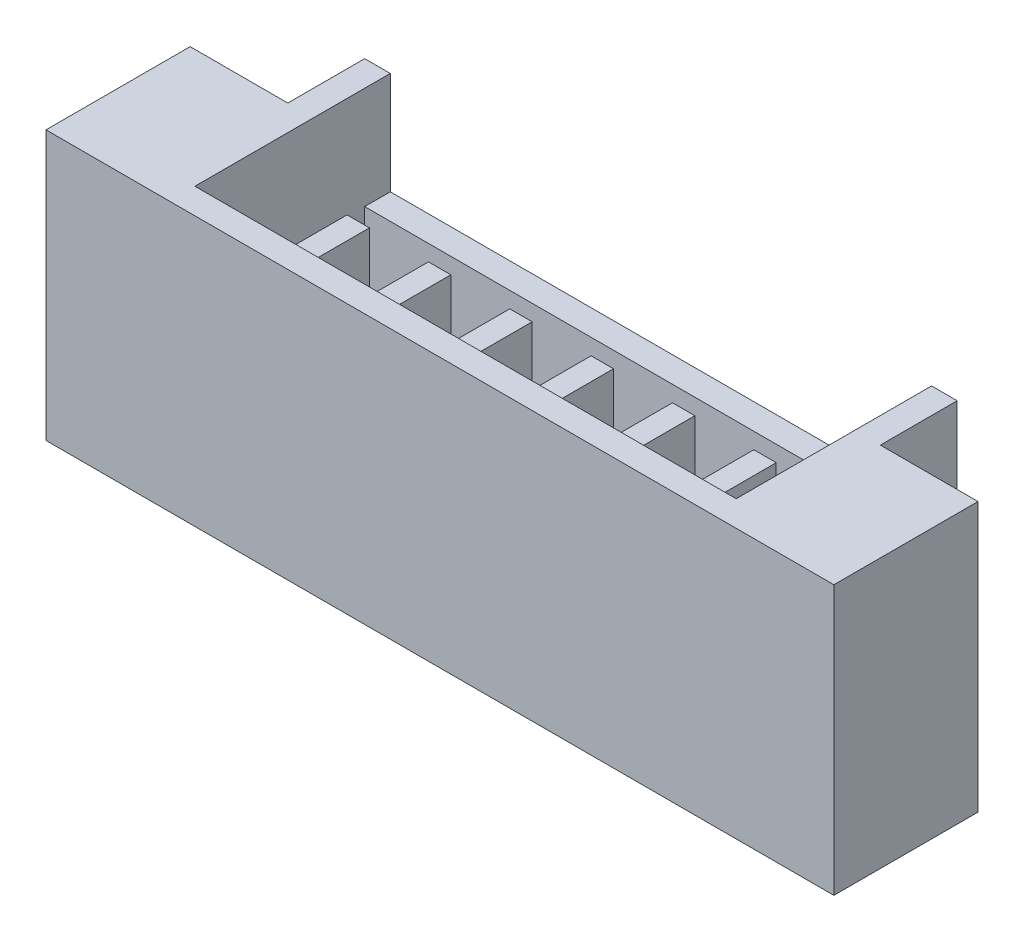
SolidWorks part; units mm, degrees
ref_plane "Front Plane" through (0, 0, 0) normal (0, 0, 1) x (1, 0, 0)
ref_plane "Top Plane" through (0, 0, 0) normal (0, 1, 0) x (1, 0, 0)
ref_plane "Right Plane" through (0, 0, 0) normal (1, 0, 0) x (0, 0, -1)
sketch "Sketch1" plane through (0, 0, 0) normal (0, 1, 0) x (1, 0, 0)
  line L0 (0, 1.725) -> (0, -1.725) construction
  line L1 (-6.15, 1.725) -> (6.15, 1.725)
  line L2 (-6.15, 1.725) -> (-6.15, -1.725)
  line L3 (-6.15, -1.725) -> (6.15, -1.725)
  line L4 (6.15, 1.725) -> (6.15, -1.725)
  line L5 (-6.15, 1.725) -> (6.15, -1.725) construction
  line L6 (-6.15, -1.725) -> (6.15, 1.725) construction
  line L8 (-6.15, -1.725) -> (6.15, -1.725)
  line L9 (-6.15, -1.725) -> (-6.15, 0.525)
  line L10 (-6.15, 0.525) -> (6.15, 0.525)
  line L11 (6.15, -1.725) -> (6.15, 0.525)
  line L12 (-6.15, -1.725) -> (6.15, 0.525) construction
  line L13 (-6.15, 0.525) -> (6.15, -1.725) construction
  line L14 (-4.625, -1.725) -> (4.625, -1.725)
  line L15 (-4.625, -1.725) -> (-4.625, 1.725)
  line L16 (-4.625, 1.725) -> (4.625, 1.725)
  line L17 (4.625, -1.725) -> (4.625, 1.725)
  line L18 (-4.625, -1.725) -> (4.625, 1.725) construction
  line L19 (-4.625, 1.725) -> (4.625, -1.725) construction
  point P0 (0, 0)
  point P8 (0, -0.6)
  point P13 (0, 0)
  dimension "D1" = 12.3
  dimension "D2" = 3.45
  dimension "D3" = 2.25
  dimension "D4" = 9.25
extrude "Boss-Extrude1" add sketch "Sketch1" along normal blind 4.2 contours L3 L15 L10 L2 | L10 L17 L1 L15 | L8 L17 L10 L15 | L17 L3 L4 L10 region at (0, 0, -1.125) region at (-5.3875, 0, 0.6) region at (0, 0, 0.6) region at (5.3875, 0, 0.6)
sketch "Sketch2" plane through (0, 4.2, 0) normal (0, 1, 0) x (1, 0, 0)
  line L0 (-4.625, 1.725) -> (4.625, 1.725) construction
  line L1 (4.225, -1.325) -> (-4.225, -1.325)
  line L2 (4.225, -1.325) -> (4.225, 1.325)
  line L3 (4.225, 1.325) -> (-4.225, 1.325)
  line L4 (-4.225, -1.325) -> (-4.225, 1.325)
  line L5 (4.225, -1.325) -> (-4.225, 1.325) construction
  line L6 (4.225, 1.325) -> (-4.225, -1.325) construction
  line L7 (-4.225, 1.325) -> (-4.225, 1.725) construction
  line L8 (-4.225, 1.325) -> (-4.625, 1.325) construction
  line L9 (-4.625, 0.525) -> (-4.625, 1.725) construction
  point P0 (0, 0)
  dimension "D1" = 0.4
extrude "Cut-Extrude1" cut sketch "Sketch2" against normal offset from surface (3.2 mm away) 1 up to face at (0, 0, -0.2625)
sketch "Sketch3" plane through (0, 4.2, 0) normal (0, 1, 0) x (1, 0, 0)
  line L0 (-4.625, 1.725) -> (4.625, 1.725) construction
  line L1 (-4.225, 1.325) -> (4.225, 1.325)
  line L2 (-4.225, 1.325) -> (-4.225, 1.725)
  line L3 (-4.225, 1.725) -> (4.225, 1.725)
  line L4 (4.225, 1.325) -> (4.225, 1.725)
  line L5 (4.225, -1.325) -> (4.225, 1.325) construction
extrude "Cut-Extrude2" cut sketch "Sketch3" against normal offset from surface (1.6 mm away) 2.6 up to face at (0, 0, -0.2625)
sketch "Sketch4" plane through (0, 1, 0) normal (0, 1, 0) x (1, 0, 0)
  line L0 (-4.225, -0.325) -> (4.225, -0.325) construction
  line L1 (-4.225, 1.725) -> (-4.225, -1.325) construction
  line L2 (4.225, -1.325) -> (4.225, 1.725) construction
  line L3 (4.225, -1.325) -> (-4.225, -1.325) construction
  line L4 (0, 1.325) -> (0, -1.325) construction
  line L5 (-4.225, 1.325) -> (4.225, 1.325) construction
  line L6 (0.46, 0.175) -> (0.46, -0.825)
  line L7 (-0.81, 0.175) -> (-0.46, 0.175)
  line L8 (-0.81, 0.175) -> (-0.81, -0.825)
  line L9 (-0.81, -0.825) -> (-0.46, -0.825)
  line L10 (-0.46, 0.175) -> (-0.46, -0.825)
  line L11 (-0.81, 0.175) -> (-0.46, -0.825) construction
  line L12 (-0.81, -0.825) -> (-0.46, 0.175) construction
  line L13 (0.46, -0.825) -> (0.81, -0.825)
  line L14 (0.81, 0.175) -> (0.81, -0.825)
  line L15 (0.46, 0.175) -> (0.81, 0.175)
  line L16 (1.73, 0.175) -> (1.73, -0.825)
  line L17 (1.73, -0.825) -> (2.08, -0.825)
  line L18 (2.08, 0.175) -> (2.08, -0.825)
  line L19 (1.73, 0.175) -> (2.08, 0.175)
  line L20 (3, 0.175) -> (3, -0.825)
  line L21 (3, -0.825) -> (3.35, -0.825)
  line L22 (3.35, 0.175) -> (3.35, -0.825)
  line L23 (3, 0.175) -> (3.35, 0.175)
  line L24 (-3, 0.175) -> (-3.35, 0.175)
  line L25 (-3.35, 0.175) -> (-3.35, -0.825)
  line L26 (-3, -0.825) -> (-3.35, -0.825)
  line L27 (-3, 0.175) -> (-3, -0.825)
  line L28 (-1.73, 0.175) -> (-2.08, 0.175)
  line L29 (-2.08, 0.175) -> (-2.08, -0.825)
  line L30 (-1.73, -0.825) -> (-2.08, -0.825)
  line L31 (-1.73, 0.175) -> (-1.73, -0.825)
  point P12 (-0.635, -0.325)
  point P17 (0, 0)
  dimension "D1" = 1
  dimension "D2" = 0.35
  dimension "D3" = 1
  dimension "D4" = 1.27
  dimension "D5" = 4
extrude "Boss-Extrude2" add sketch "Sketch4" along normal offset from surface (2.5 mm away) 0.7 up to face at (0, 4.2, -0.2417)
